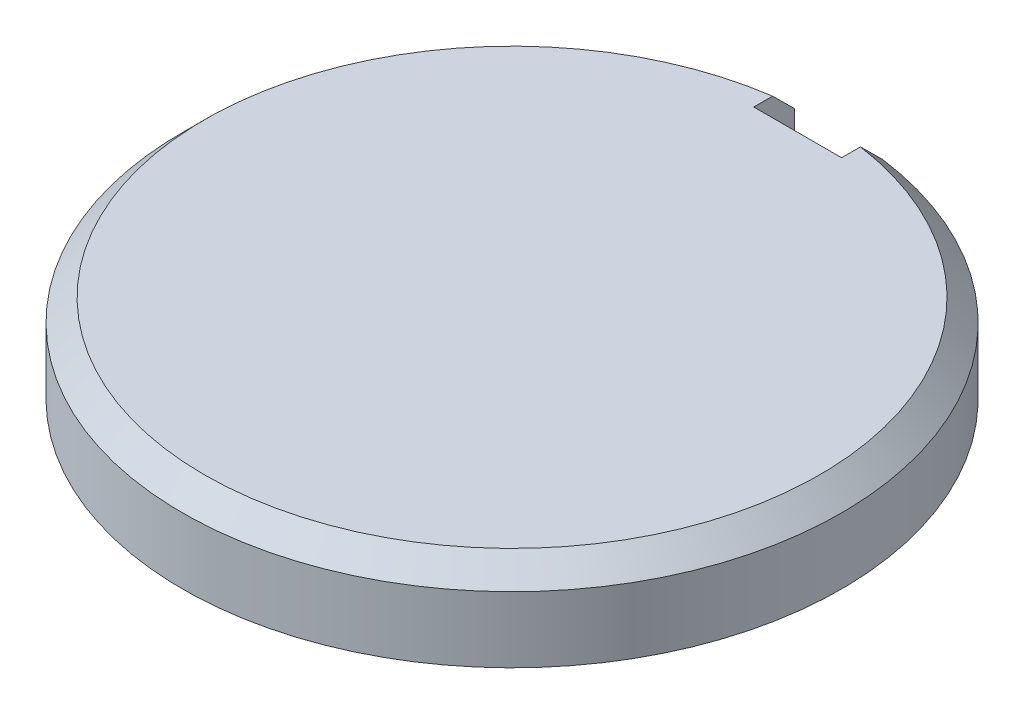
SolidWorks part; units mm, degrees
ref_plane "Front Plane" through (0, 0, 0) normal (0, 0, 1) x (1, 0, 0)
ref_plane "Top Plane" through (0, 0, 0) normal (0, 1, 0) x (1, 0, 0)
ref_plane "Right Plane" through (0, 0, 0) normal (1, 0, 0) x (0, 0, -1)
ref_plane "Plane1" through (0, 0, -62) normal (0, 0, 1) x (1, 0, 0)
sketch "Sketch1" plane through (0, 0, -62) normal (0, 0, 1) x (1, 0, 0)
  line L0 (0, 44.6) -> (0, 57.2) construction
  line L1 (2.3, 49.6) -> (2.3, 50.6)
  line L2 (2.3, 50.6) -> (0, 50.6)
  line L3 (0, 50.6) -> (0, 52.2)
  line L4 (0, 52.2) -> (5.6, 52.2)
  line L5 (5.6, 52.2) -> (6, 51.8)
  line L6 (6, 51.8) -> (6, 50.6)
  line L7 (6, 50.6) -> (3, 50.6)
  line L8 (3, 50.6) -> (3, 49.6)
  line L9 (3, 49.6) -> (2.3, 49.6)
revolve "Revolve1" add sketch "Sketch1" angle 360 about L0
sketch "Sketch2" plane through (0, 0, 0) normal (0, 0, 1) x (1, 0, 0)
  line L1 (-0.4, 49.3) -> (0.4, 49.3)
  line L2 (-0.4, 49.3) -> (-0.4, 50.58)
  line L3 (-0.4, 50.58) -> (0.4, 50.58)
  line L4 (0.4, 49.3) -> (0.4, 50.58)
extrude "Boss-Extrude1" add sketch "Sketch2" along normal blind 6.4 from offset 65.2 separate body offset against normal yes
combine bodies "Combine1" operation type subtract main body 101 bodies to subtract 102
sketch "Sketch3" plane through (0, 0, 0) normal (0, 0, 1) x (1, 0, 0)
  line L1 (-3.2, 49.3) -> (3.2, 49.3)
  line L2 (-3.2, 49.3) -> (-3.2, 50.58)
  line L3 (-3.2, 50.58) -> (3.2, 50.58)
  line L4 (3.2, 49.3) -> (3.2, 50.58)
extrude "Boss-Extrude2" add sketch "Sketch3" along normal blind 0.8 from offset 62.4 separate body offset against normal yes
combine bodies "Combine2" operation type subtract main body 103 bodies to subtract 104
sketch "Sketch4" plane through (0, 0, 0) normal (0, 0, 1) x (1, 0, 0)
  line L1 (-0.8, 50.5) -> (0.8, 50.5)
  line L2 (-0.8, 50.5) -> (-0.8, 52.3)
  line L3 (-0.8, 52.3) -> (0.8, 52.3)
  line L4 (0.8, 50.5) -> (0.8, 52.3)
extrude "Boss-Extrude3" add sketch "Sketch4" along normal blind 0.9 from offset 68.1 separate body offset against normal yes
combine bodies "Combine3" operation type subtract main body 105 bodies to subtract 106
